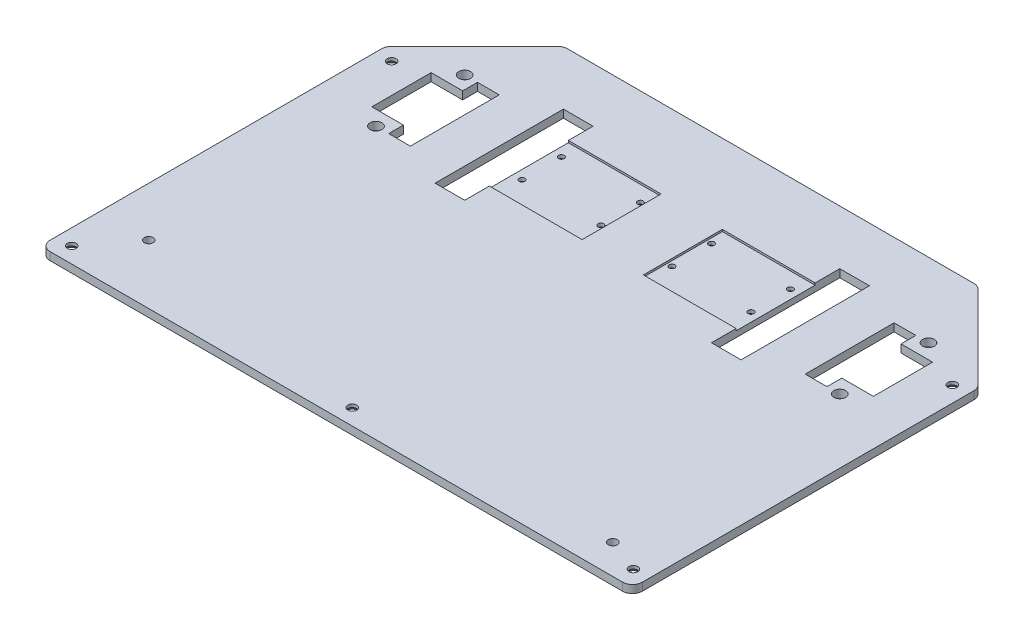
SolidWorks part; units mm, degrees
material "Acier non allié"
ref_plane "Front" through (0, 0, 0) normal (0, 0, 1) x (1, 0, 0)
ref_plane "Top" through (0, 0, 0) normal (0, 1, 0) x (1, 0, 0)
ref_plane "Right" through (0, 0, 0) normal (1, 0, 0) x (0, 0, -1)
sketch "Main scetch" plane through (0, 0, 0) normal (0, 1, 0) x (1, 0, 0)
  line L0 (-150, 0) -> (150, 0)
  line L1 (0, 0) -> (150, 0) construction
  line L2 (0, 0) -> (0, 220) construction
  line L3 (0, 220) -> (150, 220) construction
  line L4 (150, 0) -> (150, 220) construction
  line L5 (150, 0) -> (150, 175)
  line L6 (150, 175) -> (105, 220)
  line L10 (105, 220) -> (-105, 220)
  line L11 (-150, 0) -> (-150, 175)
  line L12 (-150, 175) -> (-105, 220)
  dimension "D1" = 150
  dimension "D2" = 220
  dimension "D3" = 45
  dimension "D4" = 45
extrude "Main extrusion" add sketch "Main scetch" along normal blind 4
fillet "Corner leave" radius 5 6 edges at (-150, 2, 0) (150, 2, -175) (105, 2, -220) (150, 2, 0) (-105, 2, -220) (-150, 2, -175)
sketch "Esquisse2" plane through (0, 4, 0) normal (0, 1, 0) x (1, 0, 0)
  line L0 (-145, 0) -> (145, 0) construction
  line L1 (150, 5) -> (150, 172.9289) construction
  line L2 (148.5355, 176.4645) -> (106.4645, 218.5355) construction
  line L3 (102.9289, 220) -> (-102.9289, 220) construction
  line L4 (-106.4645, 218.5355) -> (-148.5355, 176.4645) construction
  line L5 (-150, 172.9289) -> (-150, 5) construction
  line L6 (-145, 0) -> (145, 0) construction
  line L7 (150, 5) -> (150, 172.9289) construction
  line L8 (148.5355, 176.4645) -> (106.4645, 218.5355) construction
  line L9 (102.9289, 220) -> (-102.9289, 220) construction
  line L10 (-106.4645, 218.5355) -> (-148.5355, 176.4645) construction
  line L11 (-150, 172.9289) -> (-150, 5) construction
  line L12 (0, 0) -> (0, 238.9669) construction
  line L13 (0, 160) -> (165.6987, 160) construction
  line L14 (70, 230.4421) -> (70, 102.0601) construction
  line L15 (62.5, 192.5) -> (77.5, 192.5)
  line L16 (62.5, 192.5) -> (62.5, 127.5)
  line L17 (62.5, 127.5) -> (77.5, 127.5)
  line L18 (77.5, 192.5) -> (77.5, 127.5)
  line L19 (100, 137.5) -> (100, 182.5)
  line L20 (100, 182.5) -> (111, 182.5)
  line L22 (127, 175) -> (127, 145)
  line L23 (100, 137.5) -> (111, 137.5)
  line L35 (111, 182.5) -> (111, 175)
  line L36 (111, 175) -> (127, 175)
  line L37 (111, 137.5) -> (111, 145)
  line L38 (111, 145) -> (127, 145)
  line L39 (-111, 137.5) -> (-111, 145)
  line L40 (-100, 137.5) -> (-111, 137.5)
  line L41 (-100, 137.5) -> (-100, 182.5)
  line L42 (-100, 182.5) -> (-111, 182.5)
  line L43 (-111, 182.5) -> (-111, 175)
  line L44 (-111, 175) -> (-127, 175)
  line L45 (-127, 175) -> (-127, 145)
  line L46 (-111, 145) -> (-127, 145)
  line L47 (-62.5, 127.5) -> (-77.5, 127.5)
  line L48 (-77.5, 192.5) -> (-77.5, 127.5)
  line L49 (-62.5, 192.5) -> (-77.5, 192.5)
  line L50 (-62.5, 192.5) -> (-62.5, 127.5)
  circle A0 centre (117.47, 182.47) radius 3
  circle A1 centre (117.47, 137.53) radius 3
  circle A2 centre (-117.47, 137.53) radius 3
  circle A3 centre (-117.47, 182.47) radius 3
  point P28 (127, 160)
  point P29 (100, 160)
  dimension "D12" = 6
  dimension "D1" = 60
  dimension "D2" = 65
  dimension "D3" = 70
  dimension "D4" = 15
  dimension "D5" = 27
  dimension "D6" = 45
  dimension "D7" = 100
  dimension "D8" = 11
  dimension "D9" = 30
  dimension "D10" = 17.47
  dimension "D11" = 22.47
extrude "Enlèv. mat.-Extru.1" cut sketch "Esquisse2" against normal through all
sketch "Esquisse8" plane through (0, 4, 0) normal (0, 1, 0) x (1, 0, 0)
  line L0 (-150, 172.9289) -> (-150, 5) construction
  line L1 (-145, 0) -> (145, 0) construction
  line L3 (150, 5) -> (150, 172.9289) construction
  circle A0 centre (-125, 30) radius 1.5
  circle A1 centre (125, 15) radius 1.5
  circle A2 centre (-125, 12.5) radius 1
  circle A3 centre (-125, 47.5) radius 1
  dimension "D1" = 3
  dimension "D4" = 3
  dimension "D6" = 25
  dimension "D7" = 2
  dimension "D8" = 2
  dimension "D2" = 25
  dimension "D3" = 30
  dimension "D5" = 15
  dimension "D9" = 17.5
  dimension "D10" = 17.5
hole_wizard "Dégagement M41" positions "Esquisse16" profile "Esquisse17" hole size "M4" standard "ISO" end condition through all
sketch "Esquisse16" plane through (0, 4, 0) normal (0, 1, 0) x (1, 0, 0)
  point P0 (-125, 30)
  point P3 (125, 15)
sketch "Esquisse17" plane through (-125, 4, -30) normal (1, 0, 0) x (0, 0, 1)
  line L0 (0, 0) -> (0, 4)
  line L1 (0, 4) -> (2.25, 4)
  line L2 (2.25, 4) -> (2.25, 0)
  line L5 (2.25, 0) -> (0, 0)
  line L11 (0, -6.35) -> (0, 107.95) construction
  dimension "Diamètre du perçage jusqu'au prochain" = 4.5
  dimension "Profondeur du perçage jusqu'au prochain" = 4
sketch "Esquisse18" plane through (0, 4, 0) normal (0, 1, 0) x (1, 0, 0)
  line L0 (-150, 172.9289) -> (-150, 5) construction
  line L1 (-145, 0) -> (145, 0) construction
  line L3 (150, 5) -> (150, 172.9289) construction
  circle A0 centre (-142, 8) radius 1
  circle A1 centre (-142, 170) radius 1
  circle A4 centre (142, 170) radius 1
  circle A5 centre (142, 8) radius 1
  circle A6 centre (0, 8) radius 1.5
  point P6 (0, 0)
  dimension "D1" = 2
  dimension "D2" = 2
  dimension "D3" = 3
  dimension "D4" = 8
  dimension "D5" = 2
  dimension "D6" = 2
  dimension "D7" = 8
  dimension "D8" = 8
  dimension "D9" = 170
  dimension "D10" = 8
  dimension "D15" = 8
  dimension "D16" = 170
  dimension "D17" = 8
  dimension "D18" = 8
sketch "Esquisse23" plane through (0, 4, 0) normal (0, 1, 0) x (1, 0, 0)
  line L0 (-62.5, 127.5) -> (-62.5, 192.5) construction
  line L1 (-62.5, 180) -> (-15.5, 180)
  line L2 (-62.5, 180) -> (-62.5, 140)
  line L3 (-62.5, 140) -> (-15.5, 140)
  line L4 (-15.5, 180) -> (-15.5, 140)
  line L5 (102.9289, 220) -> (-102.9289, 220) construction
  dimension "D1" = 40
  dimension "D2" = 47
  dimension "D3" = 40
extrude "Enlèv. mat.-Extru.2" cut sketch "Esquisse23" against normal blind 1
sketch "Esquisse24" plane through (0, 3, 0) normal (0, 1, 0) x (1, 0, 0)
  line L0 (-58, 228.7511) -> (-58, 75.2489) construction
  line L1 (-62.5, 180) -> (-62.5, 140) construction
  line L2 (-15.5, 180) -> (-62.5, 180) construction
  line L3 (-18, 126.9657) -> (-18, 195.1017) construction
  line L4 (-58, 172) -> (-9.2469, 172) construction
  line L5 (-58, 152) -> (-13.1999, 152) construction
  circle A0 centre (-58, 172) radius 1
  circle A1 centre (-58, 152) radius 1
  circle A2 centre (-18, 172) radius 1
  circle A3 centre (-18, 152) radius 1
  dimension "D1" = 2
  dimension "D2" = 2
  dimension "D7" = 2
  dimension "D8" = 2
  dimension "D3" = 20
  dimension "D4" = 4.5
  dimension "D5" = 8
  dimension "D6" = 40
extrude "Enlèv. mat.-Extru.3" cut sketch "Esquisse24" against normal through all
hole_wizard "Fraisage pour vis à tête fraisée M2.51" positions "Esquisse27" profile "Esquisse28" countersink size "M2.5" standard "ISO" end condition through all
sketch "Esquisse27" plane through (0, 0, 0) normal (0, -1, 0) x (-1, 0, 0)
  point P0 (18, 172)
  point P3 (58, 172)
  point P6 (58, 152)
  point P9 (18, 152)
sketch "Esquisse28" plane through (-18, 0, -172) normal (1, 0, 0) x (0, 0, -1)
  line L0 (0, 0) -> (0, 4)
  line L1 (0, 4) -> (1.45, 4)
  line L2 (1.45, 4) -> (1.45, 1.3)
  line L3 (1.45, 1.3) -> (2.75, 0)
  line L5 (2.75, 0) -> (0, 0)
  line L6 (-1.45, 1.3) -> (-2.75, 0) construction
  line L11 (0, -6.35) -> (0, 107.95) construction
  dimension "Diamètre du perçage jusqu'au prochain" = 2.9
  dimension "Profondeur du perçage jusqu'au prochain" = 4
  dimension "Diamètre du fraisage entrant" = 5.5
  dimension "Angle du fraisage entrant" = 90
mirror "Symétrie1" about plane through (0, 0, 0) normal (1, 0, 0) of "Enlèv. mat.-Extru.3", "Fraisage pour vis à tête fraisée M2.51", "Enlèv. mat.-Extru.2"
hole_wizard "Fraisage pour vis à tête fraisée M41" positions "Esquisse30" profile "Esquisse31" countersink size "M4" standard "ISO" end condition through all
sketch "Esquisse30" plane through (0, 0, 0) normal (0, -1, 0) x (-1, 0, 0)
  point P0 (-142.0349, 8.4348)
  point P2 (0, 8.1016)
  point P4 (0, 8.1016)
  point P6 (142, 8)
  point P9 (142, 170)
  point P12 (-142, 170)
sketch "Esquisse31" plane through (142.0349, 0, -8.4348) normal (1, 0, 0) x (0, 0, -1)
  line L0 (0, 0) -> (0, 4)
  line L1 (0, 4) -> (2.25, 4)
  line L2 (2.25, 4) -> (2.25, 2.45)
  line L3 (2.25, 2.45) -> (4.7, 0)
  line L5 (4.7, 0) -> (0, 0)
  line L6 (-2.25, 2.45) -> (-4.7, 0) construction
  line L11 (0, -6.35) -> (0, 107.95) construction
  dimension "Diamètre du perçage jusqu'au prochain" = 4.5
  dimension "Profondeur du perçage jusqu'au prochain" = 4
  dimension "Diamètre du fraisage entrant" = 9.4
  dimension "Angle du fraisage entrant" = 90
equation "\"WIDTH\"= 300mm'Total width of the robot"
equation "\"LENGTH\"= 220mm'Total length of the robot"
equation "\"D1@Main scetch\" = \"WIDTH\" / 2"
equation "\"D2@Main scetch\" = \"LENGTH\""
equation "\"CUT_DEPTH\"= 45mm'Depth of the cut on the edges of the plate"
equation "\"D3@Main scetch\" = \"CUT_DEPTH\""
equation "\"D4@Main scetch\" = \"CUT_DEPTH\""
equation "\"Plate_th\"= 3mm'Thickness of the plate"
equation "\"D1\"= \"Plate_th\""
